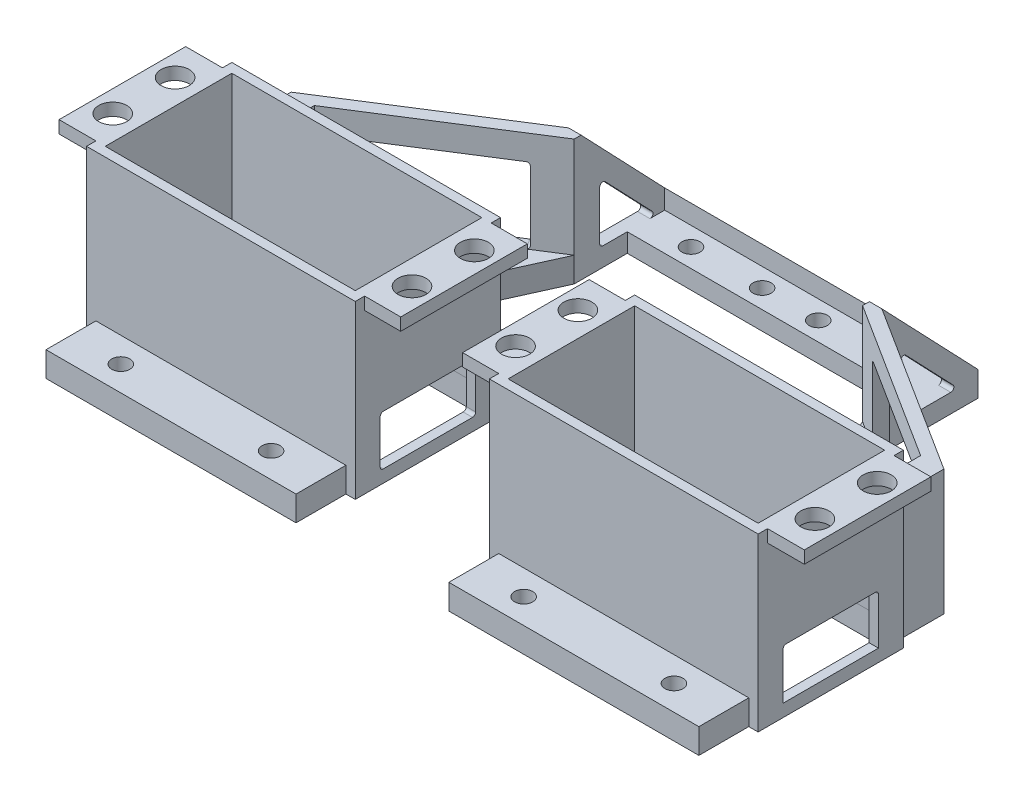
SolidWorks part; units mm, degrees
ref_plane "Front Plane" through (0, 0, 0) normal (0, 0, 1) x (1, 0, 0)
ref_plane "Top Plane" through (0, 0, 0) normal (0, 1, 0) x (1, 0, 0)
ref_plane "Right Plane" through (0, 0, 0) normal (1, 0, 0) x (0, 0, -1)
sketch "Sketch1" plane through (0, 0, 0) normal (0, 1, 0) x (1, 0, 0)
  line L0 (-59.76, 0) -> (59.76, 0) construction
  line L1 (0, -37.87) -> (0, 37.87) construction
  line L2 (-52.3548, -24.6209) -> (-52.3524, -4.3209)
  line L5 (-52.3524, -4.3209) -> (-12.2524, -4.3257)
  line L8 (-59.76, -37.87) -> (-59.76, -14.47) construction
  line L9 (-59.76, -37.87) -> (59.76, -37.87) construction
  line L10 (-59.76, -37.87) -> (-59.76, 37.87) construction
  line L11 (-59.76, 37.87) -> (59.76, 37.87) construction
  line L12 (59.76, -37.87) -> (59.76, 37.87) construction
  line L13 (-12.2524, -4.3257) -> (-12.2548, -24.6257)
  line L14 (-12.2548, -24.6257) -> (-52.3548, -24.6209)
  line L15 (-53.8522, -2.8207) -> (-10.7522, -2.8259)
  line L16 (-10.7522, -2.8259) -> (-10.755, -26.1259)
  line L17 (-10.755, -26.1259) -> (-53.855, -26.1207)
  line L18 (-53.855, -26.1207) -> (-53.8522, -2.8207)
  line L19 (-52.3524, -2.8209) -> (-52.3524, 5.1743)
  line L20 (-52.3524, 5.1743) -> (-12.2524, 5.1743)
  line L21 (-12.2524, 5.1743) -> (-12.2524, -2.8257)
  line L22 (-52.3548, -26.1209) -> (-52.3548, -34.1257)
  line L23 (-52.3548, -34.1257) -> (-12.2548, -34.1257)
  line L24 (-12.2548, -34.1257) -> (-12.2548, -26.1257)
  line L25 (-25.1261, 37.87) -> (0, 37.87)
  line L26 (-25.1261, 37.87) -> (-25.1261, 22.4543)
  line L27 (-25.1261, 22.4543) -> (-52.3524, 5.1743)
  line L28 (0, 37.87) -> (0, 35.87)
  line L29 (0, 35.87) -> (-23.1261, 35.87)
  line L30 (-23.1261, 35.87) -> (-23.1261, 21.3549)
  line L31 (-23.1261, 21.3549) -> (-48.6201, 5.1743)
  point P5 (0, 0)
  point P6 (0, 0)
  point P7 (-59.76, -14.47)
  point P22 (0, 0)
  point P32 (0, 37.87)
  point P37 (0, 0)
  line B0 (-52.3548, -24.6209) -> (-52.3524, -4.3209) construction
  line B1 (-4.9588, -4.3265) -> (-59.7588, -4.32) construction
  line B2 (-4.9612, -24.6265) -> (-4.9588, -4.3265) construction
  line B3 (-12.2548, -24.6257) -> (-12.2524, -4.3257) construction
  line B4 (-4.9612, -24.6265) -> (-59.7612, -24.62) construction
  line B5 (-59.7588, -4.32) -> (-59.7612, -24.62) construction
  circle B6 centre (-8.3042, -19.4761) radius 2.25 construction
  circle B7 centre (-8.303, -9.4761) radius 2.25 construction
  circle B8 centre (-56.303, -9.4704) radius 2.25 construction
  circle B9 centre (-56.3042, -19.4704) radius 2.25 construction
  dimension "D1" = 119.52
  dimension "D2" = 75.74
  dimension "D3" = 1.5
  dimension "D4" = 23.4
  dimension "D5" = 8
  dimension "D6" = 8
  dimension "D7" = 2
  dimension "D8" = 2
  dimension "D9" = 2
  dimension "D10" = 17.28
sketch_block_instance "Block2-1"
sketch_block "Block2"
extrude "Boss-Extrude1" add sketch "Sketch1" along normal blind 4 contours L31 L30 L29 L28 L25 L26 L27 L20 | L21 L20 L19 L15 | L18 L17 L16 L15 L13 L14 L2 L5 | L23 L24 L17 L22 region at (-53.1023, 0, 3.3108) region at (-32.3004, 0, -1.1755) region at (-38.4085, 0, -13.2932) region at (-32.3068, 0, 30.1245)
sketch "Sketch2" plane through (0, 4, 0) normal (0, 1, 0) x (1, 0, 0)
  line L1 (-48.6201, 5.1743) -> (-23.1261, 21.3549)
  line L2 (-23.1261, 21.3549) -> (-23.1261, 35.87)
  line L3 (-23.1261, 35.87) -> (0, 35.87)
  line L4 (0, 35.87) -> (0, 37.87)
  line L5 (0, 37.87) -> (-25.1261, 37.87)
  line L6 (-25.1261, 37.87) -> (-25.1261, 22.4543)
  line L7 (-25.1261, 22.4543) -> (-52.3524, 5.1743)
  line L8 (-53.8522, -2.8207) -> (-10.7522, -2.8259)
  line L9 (-10.7522, -2.8259) -> (-10.755, -26.1259)
  line L10 (-10.755, -26.1259) -> (-53.855, -26.1207)
  line L11 (-53.855, -26.1207) -> (-53.8522, -2.8207)
  line L12 (-48.6201, 5.1743) -> (-48.6201, -2.8213)
  line L13 (-52.3548, -24.6209) -> (-12.2524, -24.6209)
  line L14 (-52.3548, -24.6209) -> (-52.3548, -4.3257)
  line L15 (-52.3548, -4.3257) -> (-12.2524, -4.3257)
  line L16 (-12.2524, -24.6209) -> (-12.2524, -4.3257)
  line L17 (-52.3524, 5.1743) -> (-52.3524, -2.8209)
  line M1 (-48.6201, 5.1743) -> (-23.1261, 21.3549)
  line M2 (-23.1261, 21.3549) -> (-23.1261, 35.87)
  line M3 (-23.1261, 35.87) -> (0, 35.87)
  line M4 (0, 35.87) -> (0, 37.87)
  line M5 (0, 37.87) -> (-25.1261, 37.87)
  line M6 (-25.1261, 37.87) -> (-25.1261, 22.4543)
  line M7 (-25.1261, 22.4543) -> (-52.3524, 5.1743)
  line M8 (-52.3524, 5.1743) -> (-52.3524, -2.8209)
extrude "Boss-Extrude3" add sketch "Sketch2" along normal blind 23.5 contours L12 L8 M1 M2 M3 M4 M5 M6 M7 M8 | L8 L9 L10 L11 | L14 L15 L16 L13 region at (-49.2832, 4, -1.1765)
sketch "Sketch4" plane through (0, 27.5, 0) normal (0, 1, 0) x (1, 0, 0)
  line L0 (-52.3548, -4.3257) -> (-59.7588, -4.32)
  line L1 (-59.7588, -4.32) -> (-59.7612, -24.62)
  line L2 (-59.7612, -24.62) -> (-52.3548, -24.6209)
  line L3 (-12.2524, -4.3257) -> (-4.9588, -4.3265)
  line L4 (-4.9588, -4.3265) -> (-4.9612, -24.6265)
  line L5 (-4.9612, -24.6265) -> (-12.2524, -24.6209)
  line L6 (-12.2524, -24.6209) -> (-12.2524, -4.3257)
  line L7 (-52.3548, -24.6209) -> (-52.3548, -4.3257)
  circle A0 centre (-56.303, -9.4704) radius 2.25
  circle A1 centre (-56.3042, -19.4704) radius 2.25
  circle A2 centre (-8.303, -9.4761) radius 2.25
  circle A3 centre (-8.3042, -19.4761) radius 2.25
extrude "Boss-Extrude4" add sketch "Sketch4" against normal blind 2
sketch "Sketch5" plane through (-10.7519, 0, -0.0013) normal (1, 0, 0.0001) x (0.0001, 0, -1)
  line L1 (-22.1271, 2) -> (-6.8271, 2)
  line L2 (-22.1271, 2) -> (-22.1271, 10)
  line L3 (-22.1271, 10) -> (-6.8271, 10)
  line L4 (-6.8271, 2) -> (-6.8271, 10)
  line L6 (-26.1271, 27.5) -> (-26.1271, 0) construction
  line L7 (-2.8271, 27.5) -> (-2.8271, 0) construction
  line L8 (-4.3271, 0) -> (-24.6271, 0) construction
  dimension "D1" = 4
  dimension "D2" = 4
  dimension "D3" = 2
  dimension "D4" = 8
extrude "Cut-Extrude1" cut sketch "Sketch5" against normal through all
sketch "Sketch6" plane through (0, 4, 0) normal (0, 1, 0) x (1, 0, 0)
  line L0 (-52.3548, -34.1257) -> (-12.2548, -34.1257) construction
  line L1 (-12.2548, -34.1257) -> (-12.2548, -26.1257) construction
  line L2 (-52.3548, -26.1209) -> (-52.3548, -34.1257) construction
  line L3 (-52.3524, -2.8209) -> (-52.3524, 5.1743) construction
  line L4 (-52.3524, 5.1743) -> (-12.2524, 5.1743) construction
  line L5 (-12.2524, 5.1743) -> (-12.2524, -2.8257) construction
  circle A0 centre (-44.3548, -30.1257) radius 1.45
  circle A1 centre (-20.2548, -30.1257) radius 1.45
  circle A2 centre (-44.3524, 1.1743) radius 1.45
  circle A3 centre (-20.2524, 1.1743) radius 1.45
  dimension "D1" = 2.9
  dimension "D2" = 2.9
  dimension "D4" = 8
  dimension "D5" = 8
  dimension "D6" = 4
  dimension "D7" = 2.9
  dimension "D8" = 8
  dimension "D9" = 4
  dimension "D10" = 2.9
  dimension "D11" = 8
  dimension "D12" = 4
  dimension "D3" = 4
extrude "Cut-Extrude2" cut sketch "Sketch6" against normal through all
sketch "Sketch7" plane through (-25.1261, 0, 0) normal (-1, 0, 0) x (0, 0, 1)
  line L3 (-22.4543, 27.5) -> (-22.4543, 0) construction
  line L5 (-22.4543, 20.1314) -> (2.8207, 20.1314)
  line L8 (-37.87, 27.5) -> (2.8207, 27.5)
  line L10 (2.8207, 27.5) -> (2.8207, 20.1314)
  line L18 (-37.87, 4) -> (-22.4543, 20.1314)
  line L20 (-37.87, 27.5) -> (-37.87, 4)
extrude "Cut-Extrude3" cut sketch "Sketch7" against normal through all and the other way through all
sketch "Sketch8" plane through (-25.1261, 0, 0) normal (-1, 0, 0) x (0, 0, 1)
  line L4 (-25.4543, 12.6499) -> (-34.676, 3)
  line L6 (-25.4543, 12.6499) -> (-34.676, 3)
  line L11 (-25.4543, 3) -> (-25.4543, 12.6499)
  line L12 (-25.4543, 3) -> (-25.4543, 12.6499)
  line L14 (-34.676, 3) -> (-25.4543, 3)
  line L18 (-34.676, 3) -> (-25.4543, 3)
  dimension "D1" = 3
extrude "Cut-Extrude4" cut sketch "Sketch8" against normal up to surface (2 mm away) up to face at (-23.1261, 9.2711, -27.3808)
sketch "Sketch9" plane through (0, 0, 0) normal (0, -1, 0) x (1, 0, 0)
  line L0 (0, -35.87) -> (0, -29.87)
  line L1 (0, -29.87) -> (-23.1261, -29.87)
  line L2 (-23.1261, -35.87) -> (-23.1261, -21.3549) construction
  line L3 (-23.1261, -29.87) -> (-23.1261, -35.87)
  line L4 (-23.1261, -35.87) -> (0, -35.87)
  dimension "D1" = 6
extrude "Boss-Extrude5" add sketch "Sketch9" against normal blind 4
sketch "Sketch10" plane through (0, 4, 0) normal (0, 1, 0) x (1, 0, 0)
  line L1 (-48.6201, 5.1743) -> (-12.2524, 5.1743) construction
  line L2 (-30.4362, 5.1743) -> (-48.6201, 5.1743)
  line L6 (-30.4362, 5.1743) -> (-23.1261, 21.3549)
  line L7 (-48.6201, 5.1743) -> (-23.1261, 21.3549)
extrude "Boss-Extrude6" add sketch "Sketch10" against normal blind 4
sketch "Sketch11" plane through (0, 3, 0) normal (0, 1, 0) x (1, 0, 0)
  line L0 (0, 29.87) -> (-23.1261, 29.87) construction
  line L1 (0, 35.87) -> (0, 29.87) construction
  circle A0 centre (-15.9049, 32.87) radius 1.45
  circle A1 centre (-4.5, 32.87) radius 1.45
  dimension "D1" = 2.9
  dimension "D2" = 3
  dimension "D3" = 2.9
  dimension "D4" = 3
  dimension "D5" = 4.5
extrude "Cut-Extrude5" cut sketch "Sketch11" against normal through all and the other way through all
mirror "Mirror1" about plane through (0, 0, 0) normal (1, 0, 0) of "Boss-Extrude6", "Boss-Extrude5", "Cut-Extrude4", "Cut-Extrude3", "Cut-Extrude2", "Cut-Extrude1", "Boss-Extrude4", "Boss-Extrude3", "Boss-Extrude1", "Cut-Extrude5"
sketch "Sketch12" plane through (-17.3741, 0, -27.3744) normal (-0.5359, 0, -0.8443) x (-0.8443, 0, 0.5359)
  line L4 (37.4286, 16.1314) -> (13.1816, 16.1314)
  line L6 (37.4286, 16.1314) -> (13.1816, 16.1314)
  line L8 (37.4286, 4) -> (37.4286, 16.1314)
  line L10 (13.1816, 16.1314) -> (13.1816, 4)
  line L11 (13.1816, 4) -> (37.4286, 4)
  line L12 (37.4286, 4) -> (37.4286, 16.1314)
  line L14 (13.1816, 16.1314) -> (13.1816, 4)
  line L15 (13.1816, 4) -> (37.4286, 4)
  dimension "D1" = 4
extrude "Cut-Extrude6" cut sketch "Sketch12" against normal up to surface (2 mm away) up to face at (-35.8731, 12.0657, -13.2646)
fillet "Fillet1" radius 0.5 4 edges at (-27.9675, 4, -19.4666) (-48.4393, 4, -6.4735) (-48.4393, 16.1314, -6.4735) (-27.9675, 16.1314, -19.4666)
fillet "Fillet2" radius 0.5 3 edges at (-24.1261, 3, -34.676) (-24.1261, 3, -25.4543) (-24.1261, 12.6499, -25.4543)
fillet "Fillet3" radius 0.5 8 edges at (-11.5027, 2, 6.8258) (-11.5045, 2, 22.1258) (-11.5034, 10, 22.1258) (-11.5025, 10, 6.8258) (-53.1027, 2, 6.8208) (-53.1045, 2, 22.1208) (-53.1046, 10, 22.1208) (-53.1037, 10, 6.8208)
sketch "Sketch13" plane through (17.3741, 0, -27.3744) normal (0.5359, 0, -0.8443) x (-0.8443, 0, -0.5359)
  line L8 (-13.1816, 4) -> (-13.1816, 16.1314)
  line L9 (-13.1816, 16.1314) -> (-37.4286, 16.1314)
  line L10 (-37.4286, 16.1314) -> (-37.4286, 4)
  line L11 (-37.4286, 4) -> (-13.1816, 4)
  line L12 (-13.1816, 4) -> (-13.1816, 16.1314)
  line L14 (-37.4286, 16.1314) -> (-37.4286, 4)
  line L15 (-37.4286, 4) -> (-13.1816, 4)
  line L16 (-13.1816, 16.1314) -> (-37.4286, 16.1314)
  dimension "D1" = 4
extrude "Cut-Extrude7" cut sketch "Sketch13" against normal up to surface (2 mm away) up to face at (35.8731, 12.0657, -13.2646)
fillet "Fillet4" radius 0.5 15 edges at (12.2534, 4, 22.1257) (12.2525, 4, 6.8257) (11.5025, 10, 6.8258) (11.5034, 10, 22.1258) (52.3537, 4, 6.8209) (53.1037, 10, 6.8208) (53.1046, 10, 22.1208) (52.3546, 4, 22.1209) (48.4393, 4, -6.4735) (48.4393, 16.1314, -6.4735) (27.9675, 16.1314, -19.4666) (27.9675, 4, -19.4666) (24.1261, 3, -25.4543) (24.1261, 12.6499, -25.4543) (24.1261, 3, -34.676)
sketch "Sketch14" plane through (0, 4, 0) normal (0, 1, 0) x (1, 0, 0)
  line L6 (23.1261, 35.87) -> (-23.1261, 35.87)
  line L7 (-23.1261, 35.87) -> (-23.1261, 33.7204)
  line L8 (-23.1261, 33.7204) -> (-23.1261, 29.87)
  line L9 (-23.1261, 29.87) -> (23.1261, 29.87)
  line L10 (23.1261, 29.87) -> (23.1261, 33.7204)
  line L11 (23.1261, 33.7204) -> (23.1261, 35.87)
  line L12 (23.1261, 35.87) -> (-23.1261, 35.87)
  line L13 (-23.1261, 35.87) -> (-23.1261, 33.7204)
  line L14 (-23.1261, 33.7204) -> (-23.1261, 29.87)
  line L15 (-23.1261, 29.87) -> (23.1261, 29.87)
  line L16 (23.1261, 29.87) -> (23.1261, 33.7204)
  line L17 (23.1261, 33.7204) -> (23.1261, 35.87)
  dimension "D1" = 0
extrude "Cut-Extrude8" cut sketch "Sketch14" against normal up to surface (1 mm away) up to face at (23.9261, 3, -29.7584)
